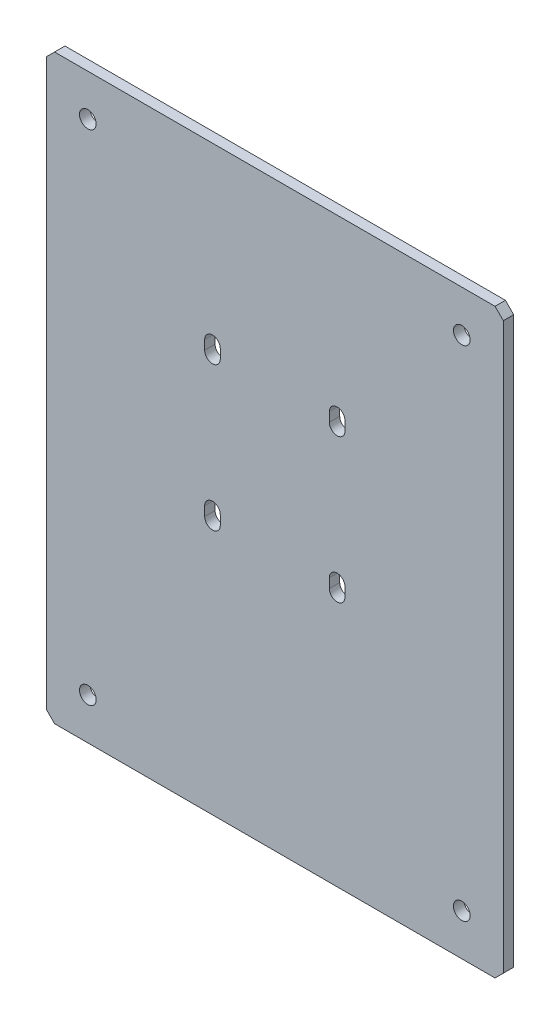
SolidWorks part; units mm, degrees
material "PC High Viscosity"
ref_plane "Front" through (0, 0, 0) normal (0, 0, 1) x (1, 0, 0)
ref_plane "Top" through (0, 0, 0) normal (0, 1, 0) x (1, 0, 0)
ref_plane "Right" through (0, 0, 0) normal (1, 0, 0) x (0, 0, -1)
sketch "Sketch1" plane through (0, 0, 0) normal (0, 0, 1) x (1, 0, 0)
  line L1 (0, 0) -> (139.7, 0)
  line L2 (0, 0) -> (0, 177.8)
  line L3 (0, 177.8) -> (139.7, 177.8)
  line L4 (139.7, 0) -> (139.7, 177.8)
extrude "Boss-Extrude1" add sketch "Sketch1" against normal blind 3.175
sketch "Sketch2" plane through (0, 0, 0) normal (0, 0, 1) x (1, 0, 0)
  line L0 (50.8, 121.7875) -> (50.8, 124.645) construction
  line L1 (48.4187, 121.7875) -> (48.4187, 124.645)
  line L2 (53.1812, 121.7875) -> (53.1812, 124.645)
  line L3 (50.8, 77.7875) -> (50.8, 80.645) construction
  line L4 (48.4187, 77.7875) -> (48.4187, 80.645)
  line L5 (53.1812, 77.7875) -> (53.1812, 80.645)
  line L12 (69.85, 0) -> (69.85, 21.0033) construction
  line L13 (0, 0) -> (139.7, 0) construction
  line L14 (88.9, 121.7875) -> (88.9, 124.645) construction
  line L15 (91.2813, 121.7875) -> (91.2813, 124.645)
  line L16 (86.5187, 121.7875) -> (86.5187, 124.645)
  line L17 (88.9, 77.7875) -> (88.9, 80.645) construction
  line L18 (91.2813, 77.7875) -> (91.2813, 80.645)
  line L19 (86.5187, 77.7875) -> (86.5187, 80.645)
  arc A0 (48.4187, 121.7875) -> (53.1812, 121.7875) centre (50.8, 121.7875) ccw
  arc A1 (53.1812, 124.645) -> (48.4187, 124.645) centre (50.8, 124.645) ccw
  arc A2 (48.4187, 77.7875) -> (53.1812, 77.7875) centre (50.8, 77.7875) ccw
  arc A3 (53.1812, 80.645) -> (48.4187, 80.645) centre (50.8, 80.645) ccw
  arc A8 (91.2813, 121.7875) -> (86.5187, 121.7875) centre (88.9, 121.7875) cw
  arc A9 (86.5187, 124.645) -> (91.2813, 124.645) centre (88.9, 124.645) cw
  arc A10 (91.2813, 77.7875) -> (86.5187, 77.7875) centre (88.9, 77.7875) cw
  arc A11 (86.5187, 80.645) -> (91.2813, 80.645) centre (88.9, 80.645) cw
  point P2 (50.8, 123.2162)
  point P9 (50.8, 79.2162)
  point P34 (88.9, 123.2162)
  point P41 (88.9, 79.2162)
  dimension "D2" = 7.62
  dimension "D5" = 44
  dimension "D6" = 77.7875
  dimension "D3" = 38.1
  dimension "D1" = 4.7625
extrude "Cut-Extrude1" cut sketch "Sketch2" against normal through all
sketch "Sketch5" plane through (0, 0, 0) normal (0, 0, 1) x (1, 0, 0)
  line L0 (0, 0) -> (139.7, 0) construction
  line L1 (0, 177.8) -> (0, 0) construction
  line L2 (139.7, 177.8) -> (0, 177.8) construction
  line L3 (139.7, 0) -> (139.7, 177.8) construction
  point P0 (12.7, 12.7)
  point P2 (12.7, 165.1)
  point P4 (127, 165.1)
  point P6 (127, 12.7)
  dimension "D1" = 12.7
  dimension "D2" = 12.7
  dimension "D3" = 12.7
  dimension "D4" = 12.7
hole_wizard "#10 Clearance Hole1" positions "Sketch5" profile "Sketch4" hole size "#10" standard "ANSI Inch" end condition through all
sketch "Sketch4" plane through (12.7, 12.7, 0) normal (1, 0, 0) x (0, -1, 0)
  line L0 (0, 0) -> (0, 3.175)
  line L1 (0, 3.175) -> (2.5527, 3.175)
  line L2 (2.5527, 3.175) -> (2.5527, 0)
  line L5 (2.5527, 0) -> (0, 0)
  line L11 (0, -6.35) -> (0, 107.95) construction
  dimension "Thru Hole Dia." = 5.1054
  dimension "Thru Hole Depth" = 3.175
chamfer "Chamfer1" distance 2.54 angle 45 4 edges at (0, 0, -1.5875) (139.7, 0, -1.5875) (139.7, 177.8, -1.5875) (0, 177.8, -1.5875)
